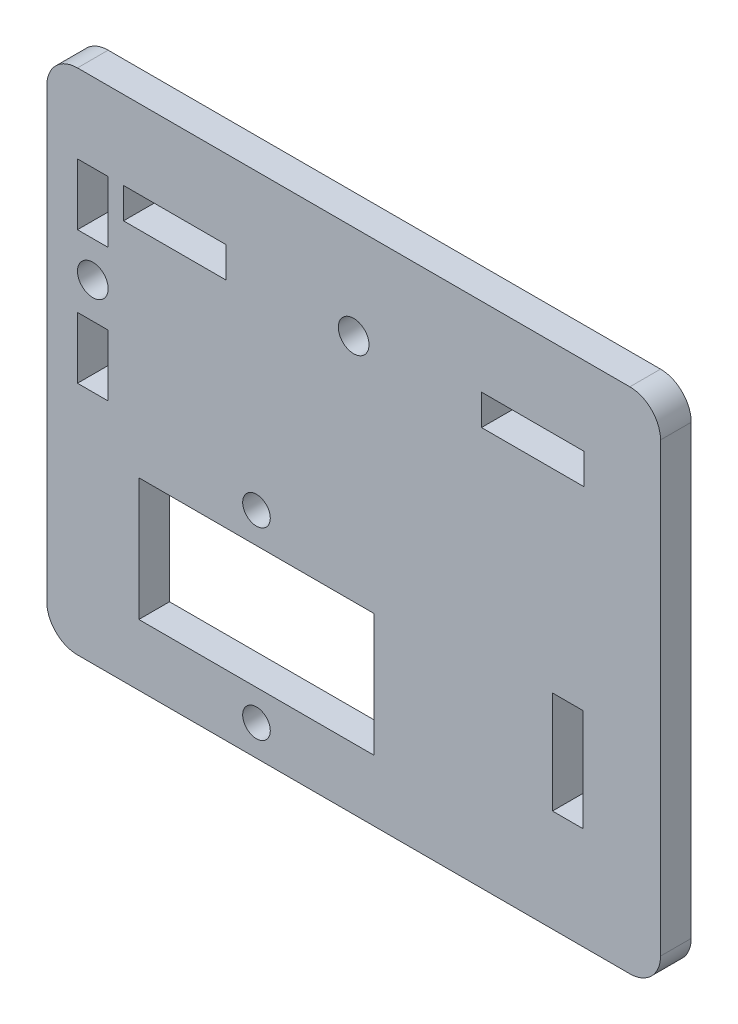
SolidWorks part; units mm, degrees
ref_plane "Front Plane" through (0, 0, 0) normal (0, 0, 1) x (1, 0, 0)
ref_plane "Top Plane" through (0, 0, 0) normal (0, 1, 0) x (1, 0, 0)
ref_plane "Right Plane" through (0, 0, 0) normal (1, 0, 0) x (0, 0, -1)
sketch "Model" plane through (0, 0, 0) normal (0, 0, 1) x (1, 0, 0)
  line L0 (77.3504, 38.9328) -> (77.3504, 61.8479)
  line L1 (77.3503, 18.1479) -> (77.3504, 38.9328)
  line L2 (74.3503, 15.1479) -> (32.8506, 15.1481)
  line L3 (17.3505, 61.8485) -> (17.3503, 19.0355)
  line L4 (23.3505, 44.1482) -> (23.3504, 38.1482)
  line L5 (20.3505, 44.1482) -> (23.3505, 44.1482)
  line L6 (20.3504, 38.1482) -> (20.3505, 44.1482)
  line L7 (23.3504, 38.1482) -> (20.3504, 38.1482)
  line L8 (23.3505, 57.1482) -> (23.3505, 51.1482)
  line L9 (20.3505, 57.1482) -> (23.3505, 57.1482)
  line L10 (20.3505, 51.1482) -> (20.3505, 57.1482)
  line L11 (23.3505, 51.1482) -> (20.3505, 51.1482)
  line L12 (49.3503, 21.148) -> (49.3504, 33.148)
  line L13 (26.3503, 21.1482) -> (49.3503, 21.148)
  line L14 (26.3504, 33.1482) -> (26.3503, 21.1482)
  line L15 (49.3504, 33.148) -> (26.3504, 33.1482)
  line L16 (34.8505, 54.1481) -> (34.8505, 57.1481)
  line L17 (24.8505, 54.1482) -> (34.8505, 54.1481)
  line L18 (24.8505, 57.1482) -> (24.8505, 54.1482)
  line L19 (34.8505, 57.1481) -> (24.8505, 57.1482)
  line L20 (69.8505, 54.1479) -> (69.8505, 57.1479)
  line L21 (59.8505, 54.1479) -> (69.8505, 54.1479)
  line L22 (59.8505, 57.148) -> (59.8505, 54.1479)
  line L23 (69.8505, 57.1479) -> (59.8505, 57.148)
  line L25 (69.7853, 25.1479) -> (66.7853, 25.1479)
  line L26 (69.7853, 25.1479) -> (69.7853, 35.1479)
  line L27 (69.7853, 35.1479) -> (66.7853, 35.1479)
  line L28 (66.7853, 25.1479) -> (66.7853, 35.1479)
  line L32 (17.3505, 61.8485) -> (17.3505, 58.8511)
  line L33 (73.8505, 64.8479) -> (20.3505, 64.8482)
  line L34 (17.3503, 19.0355) -> (17.3503, 18.1482)
  line L35 (73.8505, 64.8479) -> (74.3505, 64.8479)
  line L36 (20.3503, 15.1482) -> (32.8506, 15.1481)
  circle A1 centre (47.3505, 55.648) radius 1.5
  circle A2 centre (37.8503, 18.1481) radius 1.35
  circle A3 centre (37.8504, 36.1481) radius 1.35
  circle A4 centre (21.8505, 47.6482) radius 1.5
  arc A5 (20.3505, 64.8482) -> (17.3505, 61.8485) centre (20.3503, 61.8485) ccw
  arc A6 (17.3503, 18.1482) -> (20.3503, 15.1482) centre (20.3499, 18.1477) ccw
  arc A7 (77.3504, 61.8479) -> (74.3505, 64.8479) centre (74.3505, 61.8479) ccw
  arc A8 (74.3503, 15.1479) -> (77.3503, 18.1479) centre (74.3504, 18.1478) ccw
  dimension "D1" = 3
  dimension "D2" = 10
  dimension "D3" = 7.7
  dimension "D4" = 3
  dimension "D5" = 10
  dimension "D6" = 19
extrude "Boss-Extrude1" add sketch "Model" along normal blind 3 contours L2 A8 L1 L0 A7 L35 L33 A5 L32 L3 L34 A6 L36 L8 L11 L10 L9 L4 L7 L6 L5 L15 L12 L13 L14 L19 L16 L17 L18 L23 L20 L21 L22 region at (48.6073, 41.0229, 0)
